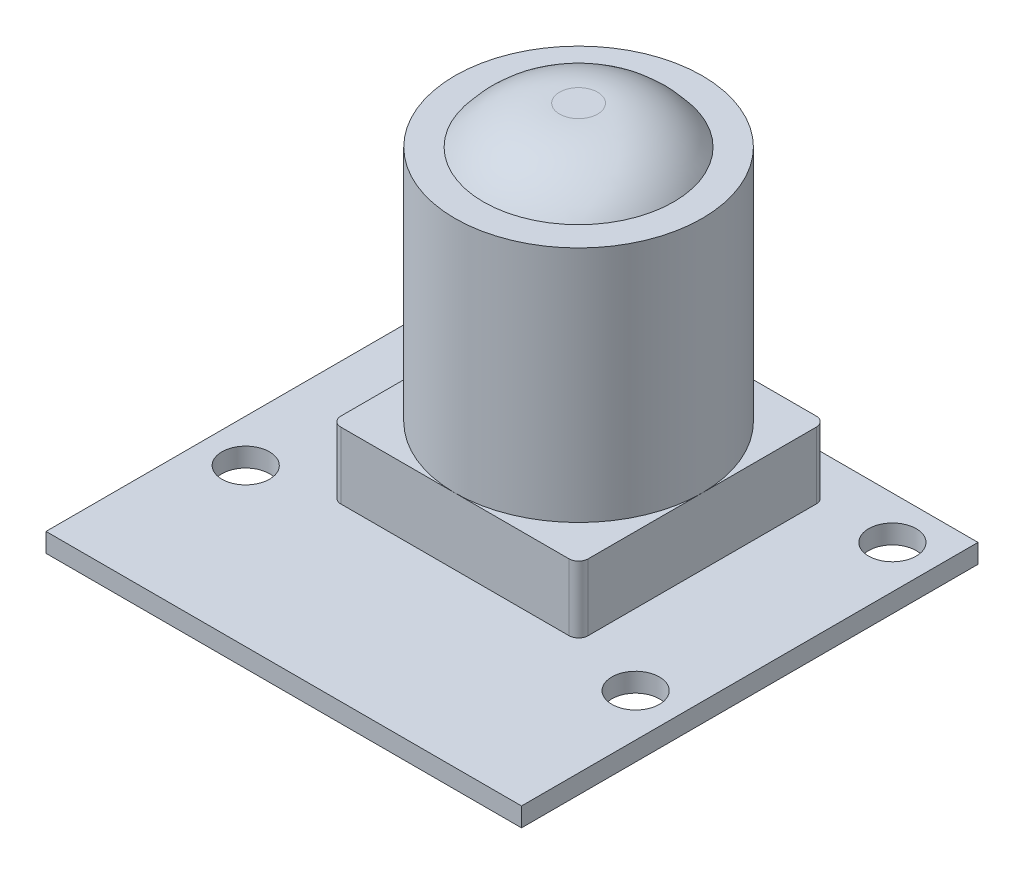
SolidWorks part; units mm, degrees
ref_plane "Спереди" through (0, 0, 0) normal (0, 0, 1) x (1, 0, 0)
ref_plane "Сверху" through (0, 0, 0) normal (0, 1, 0) x (1, 0, 0)
ref_plane "Справа" through (0, 0, 0) normal (1, 0, 0) x (0, 0, -1)
other "Configuration Table"
sketch "Эскиз1" plane through (0, 0, 0) normal (0, 1, 0) x (1, 0, 0)
  line L1 (0, 0) -> (-25, 0)
  line L2 (0, 0) -> (0, 24)
  line L3 (0, 24) -> (-25, 24)
  line L4 (-25, 0) -> (-25, 24)
  dimension "D1" = 25
  dimension "D2" = 24
extrude "Бобышка-Вытянуть1" add sketch "Эскиз1" along normal blind 1
sketch "Эскиз2" plane through (0, 1, 0) normal (0, 1, 0) x (1, 0, 0)
  circle A0 centre (-22.75, 21.75) radius 1.25
  circle A1 centre (-2.25, 21.75) radius 1.25
  circle A2 centre (-22.75, 8.25) radius 1.25
  circle A3 centre (-2.25, 8.25) radius 1.25
extrude "Вырез-Вытянуть1" cut sketch "Эскиз2" against normal through all
sketch "Эскиз3" plane through (0, 1, 0) normal (0, 1, 0) x (1, 0, 0)
  line L2 (-19, 21.5) -> (-19, 9.5)
  line L3 (-18.5, 22) -> (-6.5, 22)
  line L5 (-18.5, 9) -> (-6.5, 9)
  line L6 (-6, 21.5) -> (-6, 9.5)
  circle A0 centre (-12.5, 15.5) radius 6.5
  arc A1 (-6.5, 22) -> (-6, 21.5) centre (-6.5, 21.5) cw
  arc A2 (-6.5, 9) -> (-6, 9.5) centre (-6.5, 9.5) ccw
  arc A3 (-19, 9.5) -> (-18.5, 9) centre (-18.5, 9.5) ccw
  arc A4 (-19, 21.5) -> (-18.5, 22) centre (-18.5, 21.5) cw
  dimension "D1" = 0.5
extrude "Бобышка-Вытянуть4" add sketch "Эскиз3" along normal blind 16 contours A0
extrude "Бобышка-Вытянуть5" add sketch "Эскиз3<5>" along normal blind 3.5 contours A3 L5 A2 L6 A1 L3 A4 L2
sketch "Эскиз3<5>" plane through (0, 1, 0) normal (0, 1, 0) x (1, 0, 0) same geometry as "Эскиз3"
sketch "Эскиз5" plane through (0, 17, 0) normal (0, 1, 0) x (1, 0, 0)
  circle A0 centre (-12.5, 15.5) radius 5
extrude "Бобышка-Вытянуть6" add sketch "Эскиз5" along normal blind 2 contours A0
fillet "Скругление1" radius 5 1 edges at (-12.5, 19, -10.5)
sketch "Эскиз10" plane through (0, 0, 0) normal (0, -1, 0) x (1, 0, 0)
  line L0 (-25, -24) -> (-23, -24)
  line L1 (-23, -24) -> (-23, -14)
  line L2 (-23, -14) -> (-21.5, -14)
  line L3 (-21.5, -14) -> (-21.5, -15.5)
  line L4 (-25, -24) -> (-12.5, -24)
  line L5 (-12.5, -24) -> (-12.5, -15.1881)
  circle A0 centre (-21.5, -15.5) radius 1.5
  circle A1 centre (-3.5, -15.5) radius 1.5
extrude "Бобышка-Вытянуть7" add sketch "Эскиз10" along normal blind 1 contours A0 | A1
fillet "Скругление2" radius 1 2 edges at (-3.5, -1, -14) (-21.5, -1, -17)
